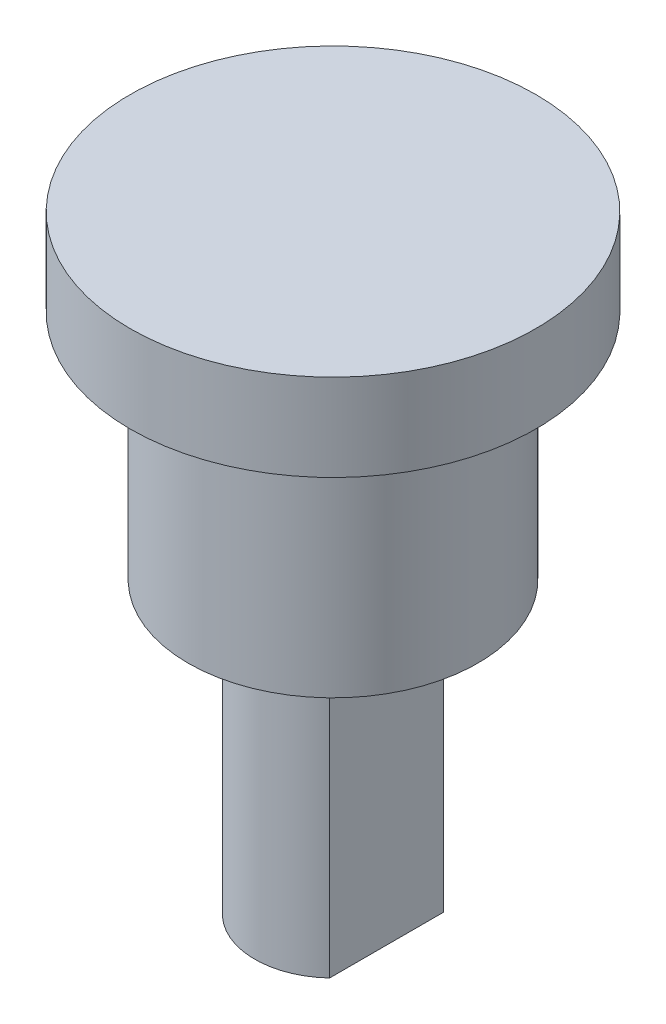
SolidWorks part; units mm, degrees
note: The reader was unsure of these and kept them because the rebuilt part matched: shared geometry of "Sketch1<3>", "Sketch1<5>".
ref_plane "Front Plane" through (0, 0, 0) normal (0, 0, 1) x (1, 0, 0)
ref_plane "Top Plane" through (0, 0, 0) normal (0, 1, 0) x (1, 0, 0)
ref_plane "Right Plane" through (0, 0, 0) normal (1, 0, 0) x (0, 0, -1)
sketch "Sketch1" plane through (0, 0, 0) normal (0, 1, 0) x (1, 0, 0)
  line L0 (1.85, 1.9666) -> (1.85, -1.9666)
  line L1 (-1.85, 1.9666) -> (-1.85, -1.9666)
  line L2 (0, 2.7) -> (0, -2.7) construction
  circle A0 centre (0, 0) radius 7
  arc A1 (1.85, 1.9666) -> (-1.85, 1.9666) centre (0, 0) ccw
  circle A2 centre (0, 0) radius 5
  arc A3 (-1.85, -1.9666) -> (1.85, -1.9666) centre (0, 0) ccw
  dimension "D1" = 5.4
  dimension "D3" = 14
  dimension "D4" = 10
  dimension "D2" = 3.7
extrude "Boss-Extrude1" add sketch "Sketch1" along normal blind 3 contours L2 A1 L1 A3 | A1 L2 A3 L0 | A2 A3 L1 A1 L0 | A0 A2
extrude "Boss-Extrude2" add sketch "Sketch1<3>" against normal blind 8 contours A1 L2 L0 | L2 A1 L1 | L0 A1 | L1 A1
sketch "Sketch1<3>" plane through (0, 0, 0) normal (0, 1, 0) x (1, 0, 0) same geometry as "Sketch1"
extrude "Boss-Extrude3" add sketch "Sketch1<5>" against normal blind 10 from surface at -8 contours L2 A1 L1 A3 | A1 L2 A3 L0 starting at face at (0, -8, 5)
sketch "Sketch1<5>" plane through (0, 0, 0) normal (0, 1, 0) x (1, 0, 0) same geometry as "Sketch1"
